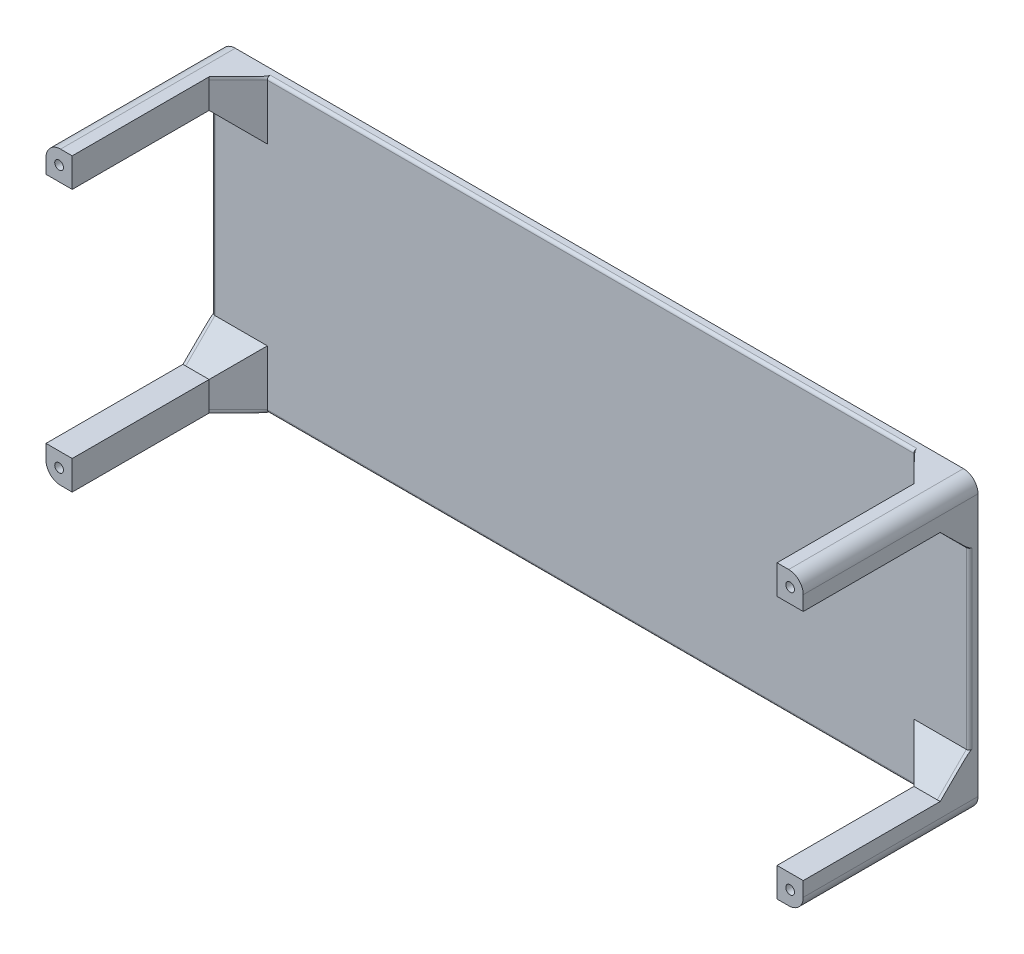
SolidWorks part; units mm, degrees
ref_plane "前视基准面" through (0, 0, 0) normal (0, 0, 1) x (1, 0, 0)
ref_plane "上视基准面" through (0, 0, 0) normal (0, 1, 0) x (1, 0, 0)
ref_plane "右视基准面" through (0, 0, 0) normal (1, 0, 0) x (0, 0, -1)
other "Configuration Table"
sketch "草图1" plane through (0, 0, 0) normal (0, 0, 1) x (1, 0, 0)
  line L1 (-130, -50) -> (130, -50)
  line L2 (-130, -50) -> (-130, 50)
  line L3 (-130, 50) -> (130, 50)
  line L4 (130, -50) -> (130, 50)
  line L5 (-130, -50) -> (130, 50) construction
  line L6 (-130, 50) -> (130, -50) construction
  point P0 (0, 0)
  dimension "D1" = 260
  dimension "D2" = 100
extrude "凸台-拉伸1" add sketch "草图1" along normal blind 3
sketch "草图2" plane through (0, 0, 0) normal (0, 0, -1) x (-1, 0, 0)
  line L0 (-125.5, 0) -> (125.5, 0) construction
  line L1 (-125.5, -45) -> (125.5, -45) construction
  line L2 (-125.5, -45) -> (-125.5, 45) construction
  line L3 (-125.5, 45) -> (125.5, 45) construction
  line L4 (125.5, -45) -> (125.5, 45) construction
  line L5 (-125.5, -45) -> (125.5, 45) construction
  line L6 (-125.5, 45) -> (125.5, -45) construction
  line L7 (0, 50) -> (0, -50) construction
  line L8 (-130, 50) -> (130, 50) construction
  line L9 (130, -50) -> (-130, -50) construction
  line L10 (121, 50) -> (130, 50)
  line L11 (121, -40) -> (130, -40)
  line L12 (121, -40) -> (121, -50)
  line L13 (121, -50) -> (130, -50)
  line L14 (130, -40) -> (130, -50)
  line L15 (121, -40) -> (130, -50) construction
  line L16 (121, -50) -> (130, -40) construction
  line L17 (130, 40) -> (130, 50)
  line L18 (121, 40) -> (130, 40)
  line L19 (121, 40) -> (121, 50)
  line L20 (-121, -50) -> (-130, -50)
  line L21 (-130, -40) -> (-130, -50)
  line L22 (-121, -40) -> (-130, -40)
  line L23 (-121, -40) -> (-121, -50)
  line L24 (-121, 40) -> (-121, 50)
  line L25 (-121, 40) -> (-130, 40)
  line L26 (-130, 40) -> (-130, 50)
  line L27 (-121, 50) -> (-130, 50)
  point P0 (0, 0)
  dimension "D1" = 251
  dimension "D2" = 90
extrude "凸台-拉伸2" add sketch "草图2" against normal blind 60
fillet "圆角3" radius 5 4 edges at (-130, -50, 30) (-130, 50, 30) (130, 50, 30) (130, -50, 30)
fillet "圆角4" radius 1 4 edges at (0, 50, 3) (-130, 0, 3) (130, 0, 3) (0, -50, 3)
sketch "草图3" plane through (0, 0, 60) normal (0, 0, 1) x (1, 0, 0)
  line L1 (-125.5, 45) -> (125.5, 45) construction
  line L2 (-125.5, 45) -> (-125.5, -45) construction
  line L3 (-125.5, -45) -> (125.5, -45) construction
  line L4 (125.5, 45) -> (125.5, -45) construction
  line L5 (-125.5, 45) -> (125.5, -45) construction
  line L6 (-125.5, -45) -> (125.5, 45) construction
  circle A0 centre (125.5, -45) radius 1.5
  circle A1 centre (125.5, 45) radius 1.5
  circle A2 centre (-125.5, -45) radius 1.5
  circle A3 centre (-125.5, 45) radius 1.5
  point P0 (0, 0)
  dimension "D3" = 3
  dimension "D4" = 3
  dimension "D5" = 3
  dimension "D6" = 3
  dimension "D1" = 90
  dimension "D2" = 251
extrude "切除-拉伸1" cut sketch "草图3" against normal blind 10
chamfer "倒角1" distance 10 angle 45 16 edges at (121, 49.7071, 2.7071) (129.7071, 40, 2.7071) (121, 44.5, 3) (125, 40, 3) (121, -49.7071, 2.7071) (129.7071, -40, 2.7071) (121, -44.5, 3) (125, -40, 3) (-121, 49.7071, 2.7071) (-129.7071, 40, 2.7071) (-121, 44.5, 3) (-125, 40, 3) (-121, -49.7071, 2.7071) (-129.7071, -40, 2.7071) (-121, -44.5, 3) (-125, -40, 3)
